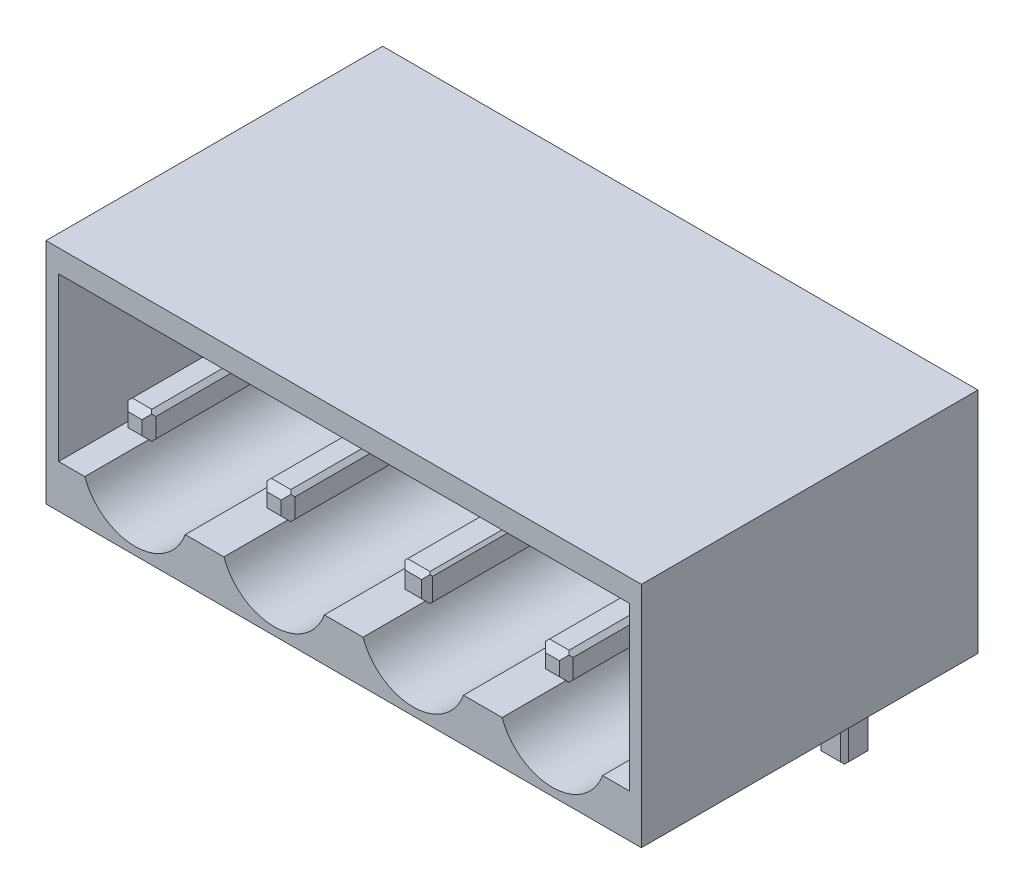
SolidWorks part; units mm, degrees
ref_plane "Спереди" through (0, 0, 0) normal (0, 0, 1) x (1, 0, 0)
ref_plane "Сверху" through (0, 0, 0) normal (0, 1, 0) x (1, 0, 0)
ref_plane "Справа" through (0, 0, 0) normal (1, 0, 0) x (0, 0, -1)
sketch "Эскиз1" plane through (0, 0, 0) normal (0, 0, 1) x (1, 0, 0)
  line L1 (-10.7, 4.1) -> (10.7, 4.1)
  line L2 (-10.7, 4.1) -> (-10.7, -4.1)
  line L3 (-10.7, -4.1) -> (10.7, -4.1)
  line L4 (10.7, 4.1) -> (10.7, -4.1)
  line L5 (-10.7, 4.1) -> (10.7, -4.1) construction
  line L6 (-10.7, -4.1) -> (10.7, 4.1) construction
  point P0 (0, 0)
  dimension "D1" = 8.2
  dimension "D2" = 21.4
extrude "Бобышка-Вытянуть1" add sketch "Эскиз1" along normal blind 12.1
sketch "Эскиз4" plane through (0, 0, 12.1) normal (0, 0, 1) x (1, 0, 0)
  circle A0 centre (-7.5, 0) radius 1.25
  circle A1 centre (-2.5, 0) radius 1.25
  circle A2 centre (2.5, 0) radius 1.25
  circle A3 centre (7.5, 0) radius 1.25
  dimension "D1" = 2.5
  dimension "D2" = 3.2
  dimension "D3" = 2
  dimension "D4" = 2
  dimension "D5" = 2
extrude "Вырез-Вытянуть3" cut sketch "Эскиз4" against normal blind 8
sketch "Эскиз5" plane through (0, 0, 12.1) normal (0, 0, 1) x (1, 0, 0)
  line L0 (-10.2456, 0) -> (-10.2456, 3.2929)
  line L1 (-10.2456, 3.2929) -> (0.2785, 3.2929)
  line L4 (-10.2456, -2.549) -> (-10.2456, 0)
  line L5 (-0.6942, -2.549) -> (0.6942, -2.549)
  line L6 (-9.3058, -2.549) -> (-10.2456, -2.549)
  line L7 (-5.6942, -2.549) -> (-4.3058, -2.549)
  line L11 (0.2785, 3.2929) -> (5.2785, 3.2929)
  line L12 (9.3058, -2.549) -> (10.2785, -2.549)
  line L13 (-0.6942, -2.549) -> (0.6942, -2.549) [skipped]
  line L14 (10.2785, 3.2929) -> (10.2785, -2.549)
  line L15 (5.2785, 3.2929) -> (10.2785, 3.2929)
  line L16 (4.3058, -2.549) -> (5.6942, -2.549)
  arc A1 (0.6942, -2.549) -> (4.3058, -2.549) centre (2.5, -1.9) ccw
  arc A2 (5.6942, -2.549) -> (9.3058, -2.549) centre (7.5, -1.9) ccw
  arc A5 (-9.3058, -2.549) -> (-5.6942, -2.549) centre (-7.5, -1.9) ccw
  arc A6 (-4.3058, -2.549) -> (-0.6942, -2.549) centre (-2.5, -1.9) ccw
  dimension "D1" = 3.2
  dimension "D2" = 2.2
  dimension "D3" = 2
  dimension "D4" = 2
  dimension "D5" = 2
extrude "Вырез-Вытянуть4" cut sketch "Эскиз5" against normal blind 7.8
sketch "Эскиз7" plane through (0, 0, 4.1) normal (0, 0, 1) x (1, 0, 0)
  line L0 (-3, 0.5) -> (-2, 0.5)
  line L1 (-8, 0.5) -> (-7, 0.5)
  line L2 (-8, 0.5) -> (-8, -0.5)
  line L3 (-8, -0.5) -> (-7, -0.5)
  line L4 (-7, 0.5) -> (-7, -0.5)
  line L5 (-8, 0.5) -> (-7, -0.5) construction
  line L6 (-8, -0.5) -> (-7, 0.5) construction
  line L7 (-3, 0.5) -> (-3, -0.5)
  line L8 (-3, -0.5) -> (-2, -0.5)
  line L9 (-2, 0.5) -> (-2, -0.5)
  line L10 (-3, 0.5) -> (-2, -0.5) construction
  line L11 (-3, -0.5) -> (-2, 0.5) construction
  line L12 (2, 0.5) -> (3, 0.5)
  line L13 (2, 0.5) -> (2, -0.5)
  line L14 (2, -0.5) -> (3, -0.5)
  line L15 (3, 0.5) -> (3, -0.5)
  line L16 (2, 0.5) -> (3, -0.5) construction
  line L17 (2, -0.5) -> (3, 0.5) construction
  line L18 (7, 0.5) -> (8, 0.5)
  line L19 (7, 0.5) -> (7, -0.5)
  line L20 (7, -0.5) -> (8, -0.5)
  line L21 (8, 0.5) -> (8, -0.5)
  line L22 (7, 0.5) -> (8, -0.5) construction
  line L23 (7, -0.5) -> (8, 0.5) construction
  point P0 (-7.5, 0)
  point P7 (-2.5, 0)
  point P12 (2.5, 0)
  point P17 (7.5, 0)
  dimension "D1" = 1
  dimension "D2" = 1
  dimension "D3" = 2
  dimension "D4" = 2
  dimension "D5" = 2
extrude "Бобышка-Вытянуть2" add sketch "Эскиз7" along normal blind 8
chamfer "Фаска1" distance 0.15 angle 45 8 edges at (-3, -0.5, 8.1) (-3, 0.5, 8.1) (-2, 0.5, 8.1) (-2, -0.5, 8.1) (-7, -0.5, 8.1) (-7, 0.5, 8.1) (-8, -0.5, 8.1) (-8, 0.5, 8.1)
chamfer "Фаска2" distance 0.25 angle 45 8 edges at (-3, 0, 12.1) (-2.5, 0.5, 12.1) (-2, 0, 12.1) (-2.5, -0.5, 12.1) (-7, 0, 12.1) (-7.5, -0.5, 12.1) (-8, 0, 12.1) (-7.5, 0.5, 12.1)
sketch "Эскиз8" plane through (0, -4.1, 0) normal (0, -1, 0) x (-1, 0, 0)
  line L0 (3, -2.1) -> (2, -2.1)
  line L1 (8, -2.1) -> (7, -2.1)
  line L2 (8, -2.1) -> (8, -1.1)
  line L3 (8, -1.1) -> (7, -1.1)
  line L4 (7, -2.1) -> (7, -1.1)
  line L5 (8, -2.1) -> (7, -1.1) construction
  line L6 (8, -1.1) -> (7, -2.1) construction
  line L7 (3, -2.1) -> (3, -1.1)
  line L8 (3, -1.1) -> (2, -1.1)
  line L9 (2, -2.1) -> (2, -1.1)
  line L10 (3, -2.1) -> (2, -1.1) construction
  line L11 (3, -1.1) -> (2, -2.1) construction
  line L12 (-2, -2.1) -> (-3, -2.1)
  line L13 (-2, -2.1) -> (-2, -1.1)
  line L14 (-2, -1.1) -> (-3, -1.1)
  line L15 (-3, -2.1) -> (-3, -1.1)
  line L16 (-2, -2.1) -> (-3, -1.1) construction
  line L17 (-2, -1.1) -> (-3, -2.1) construction
  line L18 (-7, -2.1) -> (-8, -2.1)
  line L19 (-7, -2.1) -> (-7, -1.1)
  line L20 (-7, -1.1) -> (-8, -1.1)
  line L21 (-8, -2.1) -> (-8, -1.1)
  line L22 (-7, -2.1) -> (-8, -1.1) construction
  line L23 (-7, -1.1) -> (-8, -2.1) construction
  point P0 (7.5, -1.6)
  point P7 (2.5, -1.6)
  point P12 (-2.5, -1.6)
  point P17 (-7.5, -1.6)
  dimension "D1" = 1
  dimension "D2" = 1
  dimension "D3" = 3.2
  dimension "D4" = 1.6
  dimension "D5" = 2
  dimension "D6" = 2
  dimension "D7" = 2
extrude "Бобышка-Вытянуть3" add sketch "Эскиз8" along normal blind 4
chamfer "Фаска3" distance 0.15 angle 45 16 edges at (-7, -6.1, 1.1) (-2, -6.1, 1.1) (-8, -6.1, 1.1) (-7, -6.1, 2.1) (-2, -6.1, 2.1) (-3, -6.1, 1.1) (-3, -6.1, 2.1) (-8, -6.1, 2.1) (8, -0.5, 8.1) (7, -0.5, 8.1) (8, 0.5, 8.1) (7, 0.5, 8.1) (8, -6.1, 1.1) (8, -6.1, 2.1) (7, -6.1, 1.1) (7, -6.1, 2.1)
chamfer "Фаска4" distance 0.25 angle 45 16 edges at (-2, -8.1, 1.6) (-3, -8.1, 1.6) (-2.5, -8.1, 2.1) (-2.5, -8.1, 1.1) (-8, -8.1, 1.6) (-7.5, -8.1, 2.1) (-7, -8.1, 1.6) (-7.5, -8.1, 1.1) (7.5, -8.1, 1.1) (7, -8.1, 1.6) (7.5, -8.1, 2.1) (8, -8.1, 1.6) (7.5, -0.5, 12.1) (7, 0, 12.1) (8, 0, 12.1) (7.5, 0.5, 12.1)
chamfer "Фаска6" distance 0.1 angle 45 4 edges at (2, -0.5, 8.1) (3, -0.5, 8.1) (3, 0.5, 8.1) (2, 0.5, 8.1)
chamfer "Фаска7" distance 0.2 angle 45 4 edges at (3, 0, 12.1) (2.5, -0.5, 12.1) (2, 0, 12.1) (2.5, 0.5, 12.1)
chamfer "Фаска8" distance 0.1 angle 45 4 edges at (2, -6.1, 1.1) (3, -6.1, 1.1) (2, -6.1, 2.1) (3, -6.1, 2.1)
chamfer "Фаска9" distance 0.2 angle 45 4 edges at (3, -8.1, 1.6) (2.5, -8.1, 1.1) (2, -8.1, 1.6) (2.5, -8.1, 2.1)
